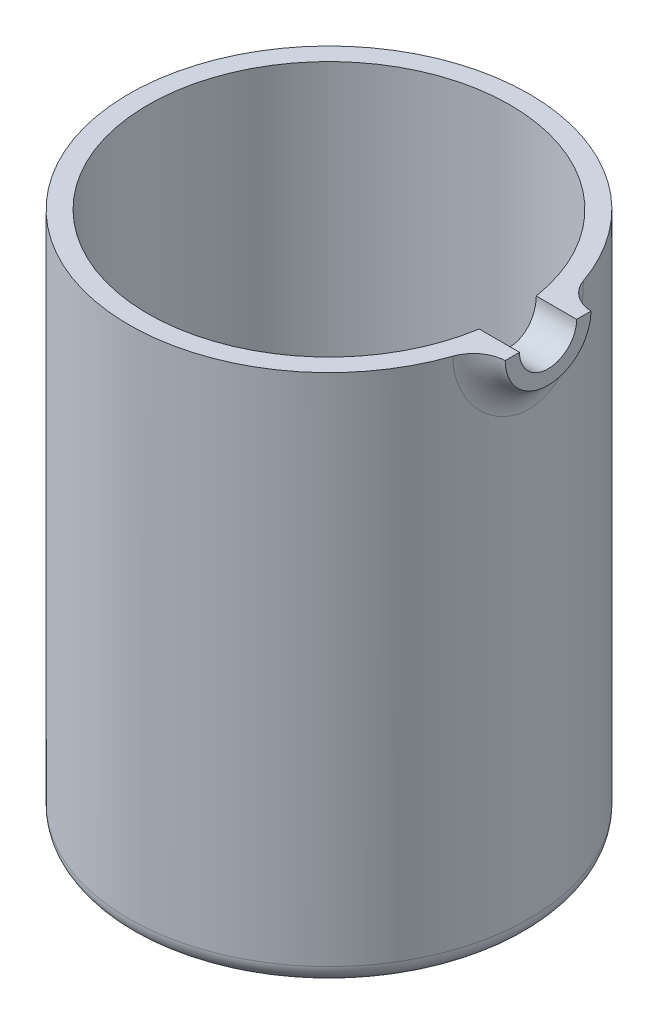
SolidWorks part; units mm, degrees
ref_plane "Front Plane" through (0, 0, 0) normal (0, 0, 1) x (1, 0, 0)
ref_plane "Top Plane" through (0, 0, 0) normal (0, 1, 0) x (1, 0, 0)
ref_plane "Right Plane" through (0, 0, 0) normal (1, 0, 0) x (0, 0, -1)
sketch "Sketch1" plane through (0, 0, 0) normal (0, 0, 1) x (1, 0, 0)
  line L0 (0, 0) -> (0, 52.5847) construction
  line L1 (0, 2) -> (19, 2)
  line L2 (19, 2) -> (19, 56)
  line L3 (19, 56) -> (21, 56)
  line L4 (21, 56) -> (21, 0)
  line L5 (21, 0) -> (0, 0)
  line L6 (0, 0) -> (0, 2)
  dimension "D1" = 42
  dimension "D2" = 56
  dimension "D3" = 2
  dimension "D4" = 2
revolve "Revolve1" add sketch "Sketch1" angle 360 about L0
fillet "Fillet1" radius 2 1 edges at (0, 0, -21)
sketch "Sketch2" plane through (0, 0, 0) normal (0, 0, 1) x (1, 0, 0)
  line L0 (21, 56) -> (19, 56) construction
  line L1 (19, 56) -> (-19, 56) construction
  line L2 (19, 53) -> (23, 53)
  line L3 (23, 53) -> (23, 51.5)
  line L4 (23, 51.5) -> (19, 51.5)
  line L5 (19, 51.5) -> (19, 53)
  dimension "D1" = 1.5
  dimension "D2" = 4
  dimension "D3" = 3
revolve "Revolve2" add sketch "Sketch2" angle 180 mid plane about L0
sketch "Sketch3" plane through (23, 0, 0) normal (1, 0, 0) x (0, 0, -1)
  circle A0 centre (0, 56) radius 3
  arc A1 (-3, 56) -> (3, 56) centre (0, 56) ccw construction
extrude "Cut-Extrude1" cut sketch "Sketch3" against normal up to next
fillet "Fillet2" radius 3.5 1 edges at (20.9947, 51.5248, 0.4719)
